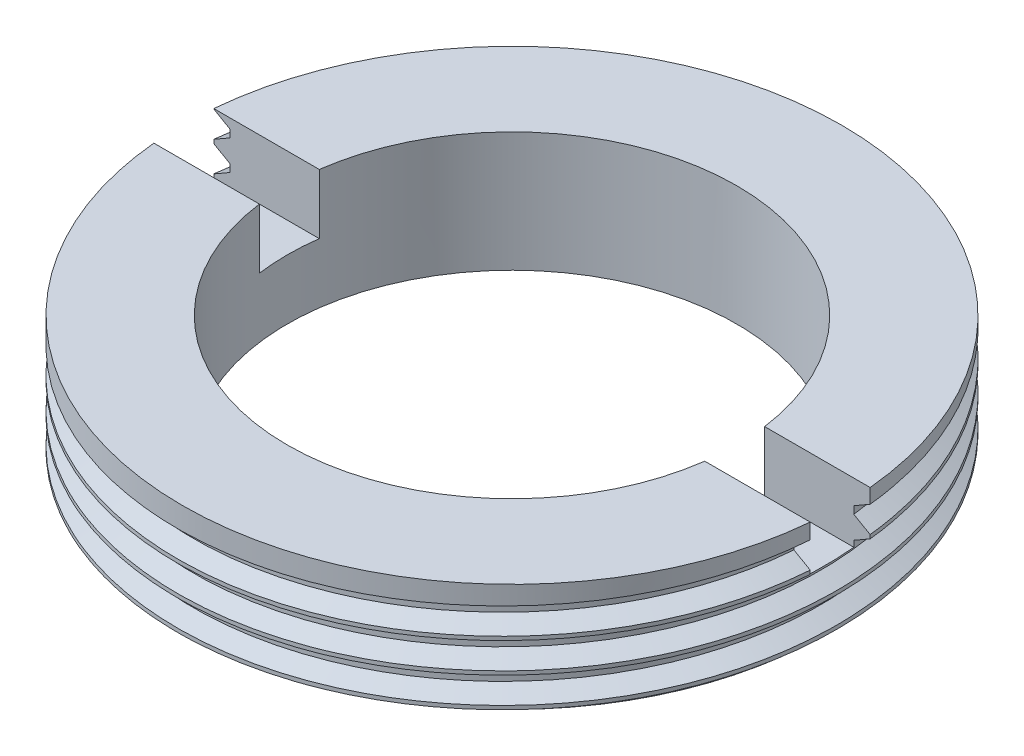
SolidWorks part; units mm, degrees
material "1060 Сплав"
ref_plane "Спереди" through (0, 0, 0) normal (0, 0, 1) x (1, 0, 0)
ref_plane "Сверху" through (0, 0, 0) normal (0, 1, 0) x (1, 0, 0)
ref_plane "Справа" through (0, 0, 0) normal (1, 0, 0) x (0, 0, -1)
sketch "Эскиз1" plane through (0, 0, 0) normal (0, 1, 0) x (1, 0, 0)
  circle A0 centre (0, 0) radius 11
  circle A1 centre (0, 0) radius 7.5
  dimension "D1" = 15
  dimension "D2" = 22
extrude "Бобышка-Вытянуть1" add sketch "Эскиз1" along normal blind 4
thread "Резьба1" pitch 1 method cut profile "Профиль резьбы1" start angle 0, offset 0, length 4, pitch 1, diameter 22
ref_plane "Плоскость1" through (-11, 4, 0) normal (0, 0, 1) x (-1, 0, 0)
sketch "Профиль резьбы1" plane through (-11, 4, 0) normal (0, 0, 1) x (-1, 0, 0)
  line L0 (0, 0) -> (0, 1) construction
  line L11 (0, 0) -> (0, 0.875)
  line L12 (0, 0.875) -> (-0.5413, 0.5625)
  line L13 (-0.5413, 0.5625) -> (-0.5413, 0.3125)
  line L15 (-0.5413, 0.3125) -> (0, 0)
  line L17 (-0.5413, 0.4375) -> (0, 0.4375) construction
  point P2 (0, 0)
  dimension "Pitch" = 1
  dimension "Profile_Angle" = 60
  dimension "Profile_Land" = 0.25
  dimension "Profile_Height" = 0.5413
sketch "Эскиз4" plane through (0, 4, 0) normal (0, 1, 0) x (1, 0, 0)
  line L1 (-12, 1) -> (12, 1)
  line L2 (-12, 1) -> (-12, -1)
  line L3 (-12, -1) -> (12, -1)
  line L4 (12, 1) -> (12, -1)
  line L5 (-12, 1) -> (12, -1) construction
  line L6 (-12, -1) -> (12, 1) construction
  point P0 (0, 0)
  dimension "D1" = 2
  dimension "D2" = 24
extrude "Вырез-Вытянуть1" cut sketch "Эскиз4" against normal blind 2
